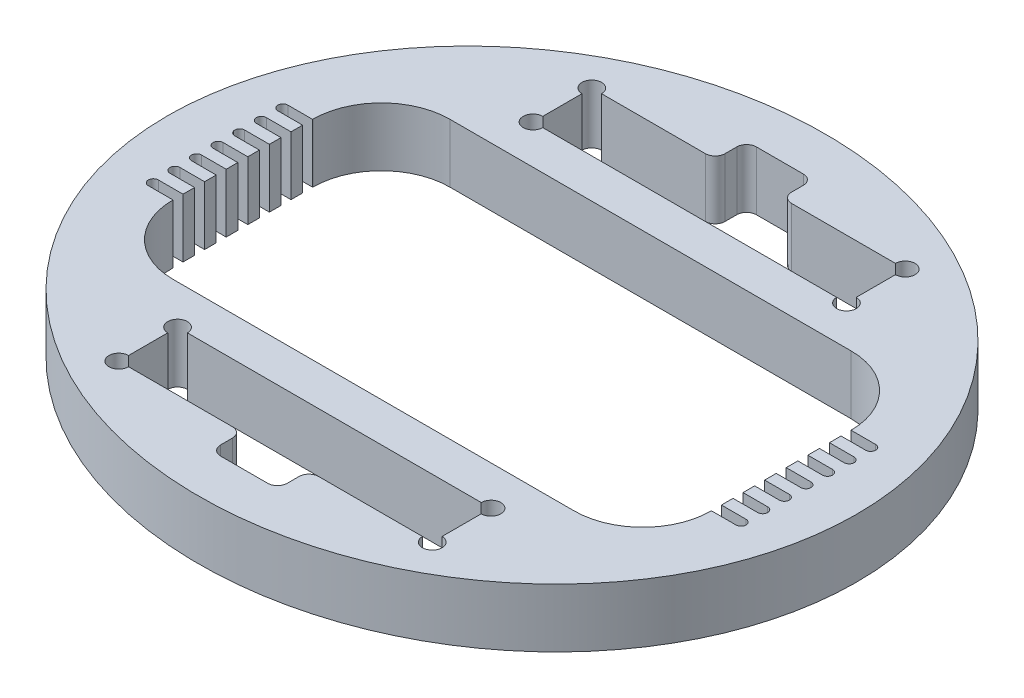
SolidWorks part; units mm, degrees
ref_plane "Front Plane" through (0, 0, 0) normal (0, 0, 1) x (1, 0, 0)
ref_plane "Top Plane" through (0, 0, 0) normal (0, 1, 0) x (1, 0, 0)
ref_plane "Right Plane" through (0, 0, 0) normal (1, 0, 0) x (0, 0, -1)
sketch "Sketch11" plane through (0, 0, 0) normal (0, 1, 0) x (1, 0, 0)
  line L1 (-32.5125, 22.4481) -> (32.5125, 22.4481)
  line L2 (-43.625, 11.3356) -> (-43.625, -11.3356)
  line L3 (-32.5125, -22.4481) -> (32.5125, -22.4481)
  line L4 (43.625, 11.3356) -> (43.625, -11.3356)
  line L5 (-43.625, 22.4481) -> (43.625, -22.4481) construction
  line L6 (-43.625, -22.4481) -> (43.625, 22.4481) construction
  arc A0 (32.5125, 22.4481) -> (43.625, 11.3356) centre (32.5125, 11.3356) cw
  arc A1 (32.5125, -22.4481) -> (43.625, -11.3356) centre (32.5125, -11.3356) ccw
  arc A2 (-43.625, -11.3356) -> (-32.5125, -22.4481) centre (-32.5125, -11.3356) ccw
  arc A3 (-32.5125, 22.4481) -> (-43.625, 11.3356) centre (-32.5125, 11.3356) ccw
  ellipse E0 centre (0, 0) end of major axis (-55.88, 0) minor radius 50.8
  point P0 (0, 0)
  dimension "D2" = 11.1125
  dimension "D1" = 87.25
extrude "Boss-Extrude4" add sketch "Sketch11" along normal blind 9.525
sketch "Sketch14" plane through (0, 9.525, 0) normal (0, 1, 0) x (1, 0, 0)
  line L0 (32.5125, 22.4481) -> (-32.5125, 22.4481) construction
  line L1 (-25.4, 38.3231) -> (-6.9814, 38.3231)
  line L2 (-25.4001, 38.323) -> (-25.4001, 28.7982)
  line L3 (-25.4, 28.7981) -> (25.4, 28.7981)
  line L4 (25.4001, 38.323) -> (25.4001, 28.7982)
  line L5 (-25.4001, 38.3231) -> (25.4001, 28.7981) construction
  line L6 (-25.4001, 28.7981) -> (25.4001, 38.3231) construction
  line L7 (6.9814, 38.3231) -> (25.4, 38.3231)
  line L9 (-5.3939, 39.9106) -> (-5.3939, 41.8156)
  line L10 (-3.8064, 43.4031) -> (3.8064, 43.4031)
  line L11 (5.3939, 39.9106) -> (5.3939, 41.8156)
  arc A0 (-25.4001, 28.7982) -> (-25.4, 28.7981) centre (-25.4, 28.7982) ccw
  arc A1 (25.4, 28.7981) -> (25.4001, 28.7982) centre (25.4, 28.7982) ccw
  arc A2 (25.4, 38.3231) -> (25.4001, 38.323) centre (25.4, 38.323) cw
  arc A3 (-25.4, 38.3231) -> (-25.4001, 38.323) centre (-25.4, 38.323) ccw
  arc A4 (-6.9814, 38.3231) -> (-5.3939, 39.9106) centre (-6.9814, 39.9106) ccw
  arc A5 (6.9814, 38.3231) -> (5.3939, 39.9106) centre (6.9814, 39.9106) cw
  arc A6 (3.8064, 43.4031) -> (5.3939, 41.8156) centre (3.8064, 41.8156) cw
  arc A7 (-5.3939, 41.8156) -> (-3.8064, 43.4031) centre (-3.8064, 41.8156) cw
  point P0 (0, 33.5606)
  point P24 (0, 43.4031)
  point P27 (-5.3939, 38.3231)
  point P34 (-5.3939, 43.4031)
  dimension "D3" = 0.0001
  dimension "D6" = 1.5875
  dimension "D1" = 9.525
  dimension "D2" = 6.35
  dimension "D4" = 50.8
  dimension "D5" = 5.08
extrude "Cut-Extrude5" cut sketch "Sketch14" against normal through all
sketch "Sketch12" plane through (0, 9.525, 0) normal (0, 1, 0) x (1, 0, 0)
  line L1 (-43.625, 0.81) -> (-47.625, 0.81)
  line L2 (-43.625, 0.81) -> (-43.625, -0.81)
  line L3 (-43.625, -0.81) -> (-47.625, -0.81)
  line L5 (-43.625, 11.3356) -> (-43.625, -11.3356) construction
  arc A0 (-47.625, 0.81) -> (-47.625, -0.81) centre (-47.625, 0) ccw
  point P6 (-43.625, 0)
  dimension "D1" = 1.62
  dimension "D2" = 4
extrude "Cut-Extrude4" cut sketch "Sketch12" against normal through all
pattern_linear "LPattern1" count 4 spacing 3.5 along (0, 0, -1) count 4 spacing 3.5 along (0, 0, 1) of "Cut-Extrude4" pattern seed only yes
mirror "Mirror1" about plane through (0, 0, 0) normal (1, 0, 0) of "LPattern1"
mirror "Mirror2" about plane through (0, 0, 0) normal (0, 0, 1) of "Cut-Extrude5"
hole_wizard "1/8 (0.125) Diameter Hole1" positions "Sketch22" profile "Sketch23" hole size "1/8" standard "ANSI Inch" end condition through all
sketch "Sketch22" plane through (0, 9.525, 0) normal (0, 1, 0) x (1, 0, 0)
  point P0 (-25.4001, 28.7982)
  point P3 (-25.4001, 38.323)
  point P6 (25.4001, 38.323)
  point P9 (25.4, 28.7981)
  point P12 (-25.4, -28.7981)
  point P15 (-25.4001, -38.323)
  point P18 (25.4, -28.7981)
  point P21 (25.4001, -38.323)
sketch "Sketch23" plane through (-25.4001, 9.525, -28.7982) normal (1, 0, 0) x (0, 0, 1)
  line L0 (0, 0) -> (0, 9.525)
  line L1 (0, 9.525) -> (1.5875, 9.525)
  line L2 (1.5875, 9.525) -> (1.5875, 0)
  line L5 (1.5875, 0) -> (0, 0)
  line L11 (0, -6.35) -> (0, 107.95) construction
  dimension "Thru Hole Dia." = 3.175
  dimension "Thru Hole Depth" = 9.525
sketch "Sketch17" [suppressed] plane through (0, 9.525, 0) normal (0, 1, 0) x (1, 0, 0)
  line L1 (12.3832, 0) -> (-86.0362, 0) construction
  line L2 (0, 0) -> (-37.589, 37.589) construction
  ellipse E1 centre (0, 0) end of major axis (-55.88, 0) minor radius 50.8 construction
  dimension "D1" = 45
sketch "Sketch21" [suppressed] plane through (0, 9.525, 0) normal (0, 1, 0) x (1, 0, 0)
  line L1 (-63.5, 63.5) -> (63.5, 63.5)
  line L2 (-63.5, 63.5) -> (-63.5, -63.5)
  line L3 (-63.5, -63.5) -> (63.5, -63.5)
  line L4 (63.5, 63.5) -> (63.5, -63.5)
  line L5 (-63.5, 63.5) -> (63.5, -63.5) construction
  line L6 (-63.5, -63.5) -> (63.5, 63.5) construction
  spline S0 degree 3 poles (62.23, -0.9874) (62.23, 3.9496) (61.7895, 7.813) (60.5103, 13.487) (59.98, 15.358) (59.0264, 18.1335) (58.682, 19.0539) (57.94, 20.8827) (57.5457, 21.783) (55.4613, 26.2158) (53.4362, 29.5449) (50.4777, 33.4468) (49.8645, 34.2141) (48.5946, 35.7223) (47.9415, 36.4588) (45.9363, 38.6096) (44.5354, 39.9687) (41.6107, 42.5439) (40.0869, 43.7598) (37.7105, 45.478) (36.9032, 46.033) (35.2582, 47.1076) (34.4188, 47.628) (30.185, 50.1181) (26.6561, 51.7721) (21.1631, 53.7767) (19.2986, 54.3649) (16.4509, 55.126) (15.4921, 55.3596) (13.575, 55.7821) (12.6147, 55.9717) (7.8048, 56.813) (3.9299, 57.1484) (-0.9471, 57.1504) (-1.9242, 57.1298) (-3.8818, 57.0459) (-4.8636, 56.9825) (-7.8057, 56.7278) (-9.7455, 56.4739) (-15.5015, 55.466) (-19.255, 54.4682) (-23.839, 52.8014) (-24.7503, 52.4469) (-26.5618, 51.6945) (-27.4644, 51.2955) (-30.1339, 50.0414) (-31.8619, 49.1304) (-36.8931, 46.1756) (-40.0448, 43.9119) (-43.716, 40.6926) (-44.4367, 40.0291) (-45.85, 38.6613) (-46.543, 37.9566) (-48.5538, 35.8063) (-49.8125, 34.3166) (-53.3444, 29.6804) (-55.3764, 26.3683) (-57.4799, 21.929) (-57.8796, 21.0234) (-58.6243, 19.203) (-58.9704, 18.2866) (-59.9309, 15.5186) (-60.4676, 13.6486) (-61.334, 9.8592) (-61.6638, 7.9397) (-61.9986, 5.0224) (-62.0835, 4.0436) (-62.1984, 2.0729) (-62.2279, 1.0876) (-62.2379, -3.8152) (-61.8111, -7.686) (-60.7432, -12.4614) (-60.5026, -13.4132) (-59.9667, -15.3105) (-59.6718, -16.2535) (-58.7163, -19.0394) (-57.9821, -20.8496) (-56.3271, -24.3795) (-55.4062, -26.0992) (-53.8858, -28.6116) (-53.3558, -29.4378) (-52.2491, -31.0676) (-51.6727, -31.8702) (-48.7072, -35.7839) (-46.0456, -38.6344) (-42.3791, -41.8684) (-41.6286, -42.4986) (-40.0934, -43.7256) (-39.3067, -44.3238) (-36.9155, -46.0531) (-35.277, -47.1223) (-30.2343, -50.091) (-26.7043, -51.7536) (-22.0839, -53.4409) (-21.1491, -53.7586) (-19.2763, -54.3489) (-18.3361, -54.6223) (-15.5043, -55.3787) (-13.6015, -55.7981) (-9.7667, -56.4708) (-7.8347, -56.724) (-4.9147, -56.9787) (-3.9377, -57.0427) (-1.9763, -57.1283) (-0.9895, -57.1499) (3.9276, -57.1504) (7.8091, -56.8115) (13.5551, -55.8076) (15.4576, -55.3897) (18.2917, -54.6348) (19.2331, -54.3618) (21.1091, -53.7719) (22.0444, -53.4547) (26.6556, -51.7742) (30.1759, -50.1196) (35.2016, -47.1695) (36.8341, -46.1076) (39.2158, -44.3915) (39.9985, -43.7989) (41.5408, -42.5711) (42.2969, -41.9385) (45.9782, -38.7029) (48.6327, -35.8651) (52.1677, -31.2251) (53.2711, -29.614) (54.8069, -27.0952) (55.3, -26.2363) (56.2334, -24.5051) (56.6751, -23.6306) (58.7602, -19.2142) (60.0367, -15.5423) (61.1247, -10.7724) (61.3166, -9.8093) (61.6478, -7.8645) (61.7865, -6.8848) (62.008, -4.9252) (62.0911, -3.9432) (62.2021, -1.9749) (62.23, -0.9874) (62.23, 3.9496) (61.7895, 7.813) knots -0.007812 -0.007812 0 0 0.03125 0.03125 0.046875 0.046875 0.054688 0.054688 0.0625 0.0625 0.09375 0.09375 0.101563 0.101563 0.109375 0.109375 0.125 0.125 0.140625 0.140625 0.148438 0.148438 0.15625 0.15625 0.1875 0.1875 0.203125 0.203125 0.210938 0.210938 0.21875 0.21875 0.25 0.25 0.257813 0.257813 0.265625 0.265625 0.28125 0.28125 0.3125 0.3125 0.320313 0.320313 0.328125 0.328125 0.34375 0.34375 0.375 0.375 0.382813 0.382813 0.390625 0.390625 0.40625 0.40625 0.4375 0.4375 0.445313 0.445313 0.453125 0.453125 0.46875 0.46875 0.484375 0.484375 0.492188 0.492188 0.5 0.5 0.53125 0.53125 0.539063 0.539063 0.546875 0.546875 0.5625 0.5625 0.578125 0.578125 0.585938 0.585938 0.59375 0.59375 0.625 0.625 0.632813 0.632813 0.640625 0.640625 0.65625 0.65625 0.6875 0.6875 0.695313 0.695313 0.703125 0.703125 0.71875 0.71875 0.734375 0.734375 0.742188 0.742188 0.75 0.75 0.78125 0.78125 0.796875 0.796875 0.804688 0.804688 0.8125 0.8125 0.84375 0.84375 0.859375 0.859375 0.867188 0.867188 0.875 0.875 0.90625 0.90625 0.921875 0.921875 0.929688 0.929688 0.9375 0.9375 0.96875 0.96875 0.976563 0.976563 0.984375 0.984375 0.992188 0.992188 1 1 1.03125 1.03125 1.046875 only from (62.23, 0) to (62.23, 0)
  spline S1 degree 3 poles (62.23, -0.9874) (62.23, 3.9496) (61.7895, 7.813) (60.5103, 13.487) (59.98, 15.358) (59.0264, 18.1335) (58.682, 19.0539) (57.94, 20.8827) (57.5457, 21.783) (55.4613, 26.2158) (53.4362, 29.5449) (50.4777, 33.4468) (49.8645, 34.2141) (48.5946, 35.7223) (47.9415, 36.4588) (45.9363, 38.6096) (44.5354, 39.9687) (41.6107, 42.5439) (40.0869, 43.7598) (37.7105, 45.478) (36.9032, 46.033) (35.2582, 47.1076) (34.4188, 47.628) (30.185, 50.1181) (26.6561, 51.7721) (21.1631, 53.7767) (19.2986, 54.3649) (16.4509, 55.126) (15.4921, 55.3596) (13.575, 55.7821) (12.6147, 55.9717) (7.8048, 56.813) (3.9299, 57.1484) (-0.9471, 57.1504) (-1.9242, 57.1298) (-3.8818, 57.0459) (-4.8636, 56.9825) (-7.8057, 56.7278) (-9.7455, 56.4739) (-15.5015, 55.466) (-19.255, 54.4682) (-23.839, 52.8014) (-24.7503, 52.4469) (-26.5618, 51.6945) (-27.4644, 51.2955) (-30.1339, 50.0414) (-31.8619, 49.1304) (-36.8931, 46.1756) (-40.0448, 43.9119) (-43.716, 40.6926) (-44.4367, 40.0291) (-45.85, 38.6613) (-46.543, 37.9566) (-48.5538, 35.8063) (-49.8125, 34.3166) (-53.3444, 29.6804) (-55.3764, 26.3683) (-57.4799, 21.929) (-57.8796, 21.0234) (-58.6243, 19.203) (-58.9704, 18.2866) (-59.9309, 15.5186) (-60.4676, 13.6486) (-61.334, 9.8592) (-61.6638, 7.9397) (-61.9986, 5.0224) (-62.0835, 4.0436) (-62.1984, 2.0729) (-62.2279, 1.0876) (-62.2379, -3.8152) (-61.8111, -7.686) (-60.7432, -12.4614) (-60.5026, -13.4132) (-59.9667, -15.3105) (-59.6718, -16.2535) (-58.7163, -19.0394) (-57.9821, -20.8496) (-56.3271, -24.3795) (-55.4062, -26.0992) (-53.8858, -28.6116) (-53.3558, -29.4378) (-52.2491, -31.0676) (-51.6727, -31.8702) (-48.7072, -35.7839) (-46.0456, -38.6344) (-42.3791, -41.8684) (-41.6286, -42.4986) (-40.0934, -43.7256) (-39.3067, -44.3238) (-36.9155, -46.0531) (-35.277, -47.1223) (-30.2343, -50.091) (-26.7043, -51.7536) (-22.0839, -53.4409) (-21.1491, -53.7586) (-19.2763, -54.3489) (-18.3361, -54.6223) (-15.5043, -55.3787) (-13.6015, -55.7981) (-9.7667, -56.4708) (-7.8347, -56.724) (-4.9147, -56.9787) (-3.9377, -57.0427) (-1.9763, -57.1283) (-0.9895, -57.1499) (3.9276, -57.1504) (7.8091, -56.8115) (13.5551, -55.8076) (15.4576, -55.3897) (18.2917, -54.6348) (19.2331, -54.3618) (21.1091, -53.7719) (22.0444, -53.4547) (26.6556, -51.7742) (30.1759, -50.1196) (35.2016, -47.1695) (36.8341, -46.1076) (39.2158, -44.3915) (39.9985, -43.7989) (41.5408, -42.5711) (42.2969, -41.9385) (45.9782, -38.7029) (48.6327, -35.8651) (52.1677, -31.2251) (53.2711, -29.614) (54.8069, -27.0952) (55.3, -26.2363) (56.2334, -24.5051) (56.6751, -23.6306) (58.7602, -19.2142) (60.0367, -15.5423) (61.1247, -10.7724) (61.3166, -9.8093) (61.6478, -7.8645) (61.7865, -6.8848) (62.008, -4.9252) (62.0911, -3.9432) (62.2021, -1.9749) (62.23, -0.9874) (62.23, 3.9496) (61.7895, 7.813) knots -0.007812 -0.007812 0 0 0.03125 0.03125 0.046875 0.046875 0.054688 0.054688 0.0625 0.0625 0.09375 0.09375 0.101563 0.101563 0.109375 0.109375 0.125 0.125 0.140625 0.140625 0.148438 0.148438 0.15625 0.15625 0.1875 0.1875 0.203125 0.203125 0.210938 0.210938 0.21875 0.21875 0.25 0.25 0.257813 0.257813 0.265625 0.265625 0.28125 0.28125 0.3125 0.3125 0.320313 0.320313 0.328125 0.328125 0.34375 0.34375 0.375 0.375 0.382813 0.382813 0.390625 0.390625 0.40625 0.40625 0.4375 0.4375 0.445313 0.445313 0.453125 0.453125 0.46875 0.46875 0.484375 0.484375 0.492188 0.492188 0.5 0.5 0.53125 0.53125 0.539063 0.539063 0.546875 0.546875 0.5625 0.5625 0.578125 0.578125 0.585938 0.585938 0.59375 0.59375 0.625 0.625 0.632813 0.632813 0.640625 0.640625 0.65625 0.65625 0.6875 0.6875 0.695313 0.695313 0.703125 0.703125 0.71875 0.71875 0.734375 0.734375 0.742188 0.742188 0.75 0.75 0.78125 0.78125 0.796875 0.796875 0.804688 0.804688 0.8125 0.8125 0.84375 0.84375 0.859375 0.859375 0.867188 0.867188 0.875 0.875 0.90625 0.90625 0.921875 0.921875 0.929688 0.929688 0.9375 0.9375 0.96875 0.96875 0.976563 0.976563 0.984375 0.984375 0.992188 0.992188 1 1 1.03125 1.03125 1.046875 only from (62.23, 0) to (62.23, 0)
  point P0 (0, 0)
  dimension "D2" = 127
  dimension "D3" = 127
  dimension "D1" = 6.35
extrude "Boss-Extrude6" [suppressed] add sketch "Sketch21" against normal blind 9.525 separate body
ref_plane "Plane1" [suppressed] through (-37.589, 9.525, -37.589) normal (-0.7071, 0, -0.7071) x (-0.7071, 0, 0.7071)
sketch "Sketch24" [suppressed] plane through (-37.589, 9.525, -37.589) normal (-0.7071, 0, -0.7071) x (-0.7071, 0, 0.7071)
  line L0 (-3.5254, 0) -> (-3.5254, -9.525) construction
  circle A0 centre (0, -4.7625) radius 1.5875
  point P4 (-3.5254, -4.7625)
  dimension "D1" = 3.175
extrude "Boss-Extrude7" [suppressed] add sketch "Sketch24" along normal blind 6.477 and the other way blind 2
sketch "Sketch25" [suppressed] plane through (0, 0, 0) normal (1, 0, 0) x (0, 0, -1)
  line L0 (0, 0) -> (0, 50000) construction
pattern_circular "CirPattern8" [suppressed] count 4 over 360 about axis through (0, 0, 0) along (0, 1, 0) of bodies 119
